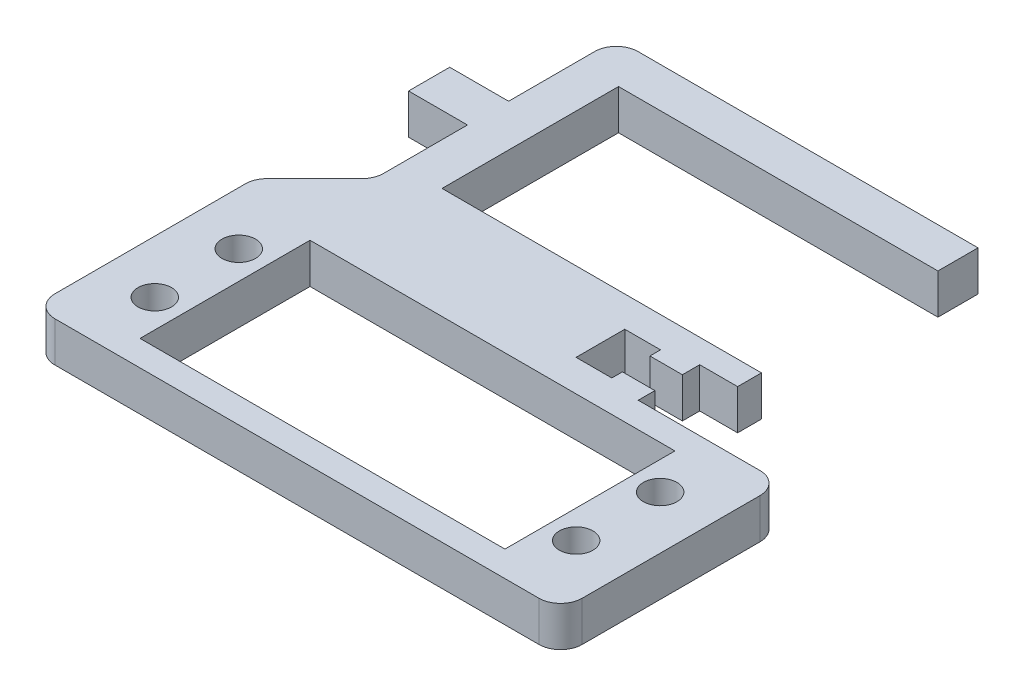
SolidWorks part; units mm, degrees
material "Custom Plastic"
ref_plane "Front Plane" through (0, 0, 0) normal (0, 0, 1) x (1, 0, 0)
ref_plane "Top Plane" through (0, 0, 0) normal (0, 1, 0) x (1, 0, 0)
ref_plane "Right Plane" through (0, 0, 0) normal (1, 0, 0) x (0, 0, -1)
sketch "Sketch1" plane through (0, 0, 0) normal (0, 1, 0) x (1, 0, 0)
  line L0 (14.097, 12.9667) -> (14.097, 14.9225)
  line L1 (-21.3995, -9.9695) -> (21.3995, -9.9695)
  line L2 (-21.3995, -9.9695) -> (-21.3995, 9.9695)
  line L3 (-21.3995, 9.9695) -> (21.3995, 9.9695)
  line L4 (21.3995, -9.9695) -> (21.3995, 9.9695)
  line L5 (-21.3995, -9.9695) -> (21.3995, 9.9695) construction
  line L6 (-21.3995, 9.9695) -> (21.3995, -9.9695) construction
  line L7 (-30.9245, 12.9667) -> (30.9245, 12.9667)
  line L8 (-30.9245, 12.9667) -> (-30.9245, -12.9667)
  line L9 (-30.9245, -12.9667) -> (30.9245, -12.9667)
  line L10 (30.9245, 12.9667) -> (30.9245, -12.9667)
  line L11 (-30.9245, 12.9667) -> (30.9245, -12.9667) construction
  line L12 (-30.9245, -12.9667) -> (30.9245, 12.9667) construction
  line L13 (14.097, 14.9225) -> (10.287, 14.9225)
  line L14 (10.287, 14.9225) -> (10.287, 13.6779)
  line L15 (10.287, 13.6779) -> (6.096, 13.6779)
  line L16 (6.096, 13.6779) -> (6.096, 19.3929)
  line L17 (6.096, 19.3929) -> (10.287, 19.3929)
  line L18 (10.287, 19.3929) -> (10.287, 18.1483)
  line L19 (10.287, 18.1483) -> (14.097, 18.1483)
  line L20 (14.097, 18.1483) -> (14.097, 20.1803)
  line L21 (14.097, 20.1803) -> (18.542, 20.1803)
  line L22 (18.542, 20.1803) -> (18.542, 22.9743)
  line L23 (18.542, 22.9743) -> (-18.923, 22.9743)
  line L24 (-30.9245, 12.9667) -> (-23.876, 20.0152)
  line L25 (-23.876, 20.0152) -> (-23.876, 30.9118)
  line L26 (-23.876, 30.9118) -> (-30.7848, 30.9118)
  line L27 (-30.7848, 30.9118) -> (-30.7848, 35.7378)
  line L28 (-30.7848, 35.7378) -> (-23.876, 35.7378)
  line L29 (-23.876, 35.7378) -> (-23.876, 48.3743)
  line L30 (-23.876, 48.3743) -> (18.542, 48.3743)
  line L31 (18.542, 48.3743) -> (18.542, 43.6753)
  line L32 (18.542, 43.6753) -> (-18.923, 43.6753)
  line L33 (-18.923, 43.6753) -> (-18.923, 22.9743)
  line L34 (-30.9245, 12.9667) -> (14.097, 12.9667)
  line L35 (-18.923, 33.3248) -> (-30.7848, 33.3248) construction
  line L36 (-18.923, 22.9743) -> (-23.876, 22.9743) construction
  line L37 (-21.3995, 9.9695) -> (-21.3995, 22.9743) construction
  line L39 (-24.7117, -4.9251) -> (24.7117, -4.9251) construction
  line L40 (-24.7117, -4.9251) -> (-24.7117, 4.9251) construction
  line L41 (-24.7117, 4.9251) -> (24.7117, 4.9251) construction
  line L42 (24.7117, -4.9251) -> (24.7117, 4.9251) construction
  line L43 (-24.7117, -4.9251) -> (24.7117, 4.9251) construction
  line L44 (-24.7117, 4.9251) -> (24.7117, -4.9251) construction
  circle A0 centre (24.7117, 4.9251) radius 1.9685
  circle A1 centre (24.7117, -4.9251) radius 1.9685
  circle A2 centre (-24.7117, -4.9251) radius 1.9685
  circle A3 centre (-24.7117, 4.9251) radius 1.9685
  point P0 (0, 0)
  point P6 (0, 0)
  point P38 (0, 0)
  dimension "D22" = 3.937
  dimension "D1" = 42.799
  dimension "D2" = 19.939
  dimension "D3" = 61.849
  dimension "D4" = 2.9972
  dimension "D5" = 13.0048
  dimension "D6" = 4.699
  dimension "D7" = 4.953
  dimension "D8" = 20.701
  dimension "D9" = 4.826
  dimension "D10" = 11.8618
  dimension "D11" = 2.794
  dimension "D12" = 4.953
  dimension "D13" = 5.715
  dimension "D14" = 4.826
  dimension "D15" = 42.418
  dimension "D16" = 3.81
  dimension "D17" = 4.191
  dimension "D18" = 37.973
  dimension "D19" = 45
  dimension "D20" = 9.8501
  dimension "D21" = 49.4233
extrude "Boss-Extrude1" add sketch "Sketch1" along normal blind 4.699 contours L1 L4 L3 L2 | L24 L25 L26 L27 L28 L29 L30 L31 L32 L33 L23 L22 L21 L20 L19 L18 L17 L16 L15 L14 L13 L0 L34 | L8 L9 L10 L7 region at (0, 0, 0)
fillet "Fillet1" radius 2.54 6 edges at (-23.876, 2.3495, -48.3743) (-23.876, 2.3495, -20.0152) (-30.9245, 2.3495, -12.9667) (-30.9245, 2.3495, 12.9667) (30.9245, 2.3495, 12.9667) (30.9245, 2.3495, -12.9667)
extrude "Cut-Extrude2" cut sketch "Sketch1<3>" against normal through all and the other way through all contours A2 | A1 | A0 | A3 region at (24.7117, 0, -4.9251) region at (24.7117, 0, 4.9251) region at (-24.7117, 0, 4.9251)
sketch "Sketch1<3>" plane through (0, 0, 0) normal (0, 1, 0) x (1, 0, 0) same geometry as "Sketch1"
sketch "Sketch2" plane through (-30.7848, 0, 0) normal (-1, 0, 0) x (0, 0, 1)
  line L0 (-35.7378, 4.699) -> (-30.9118, 0) construction
  line L1 (-35.7378, 0) -> (-30.9118, 4.699) construction
  circle A1 centre (-33.3248, 2.3495) radius 3.3679 construction
